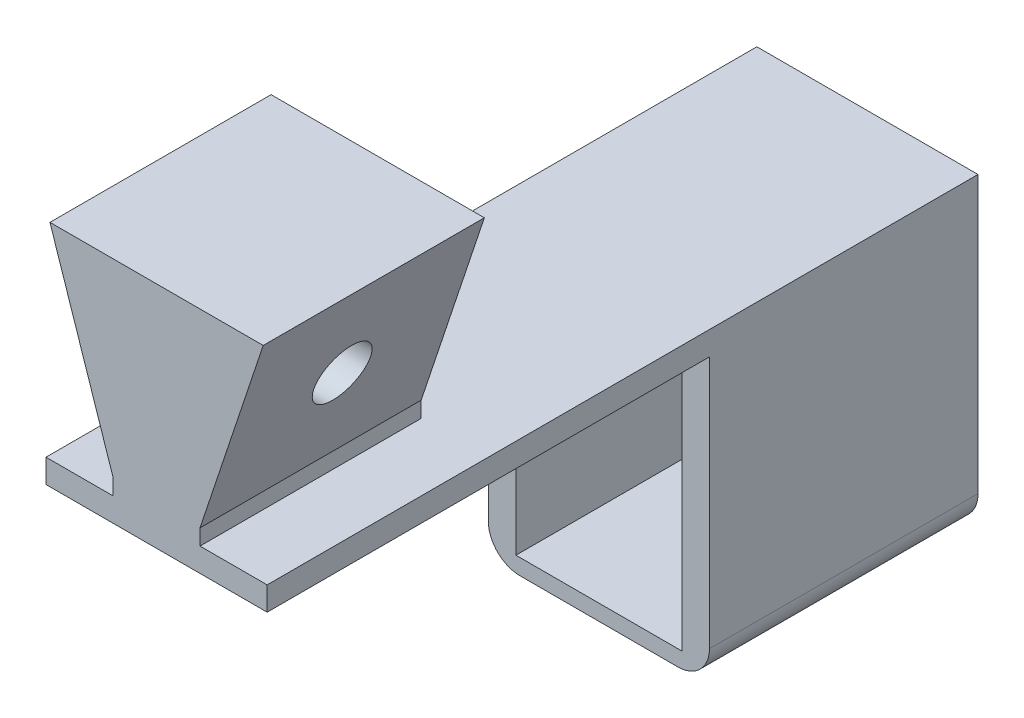
SolidWorks part; units mm, degrees
ref_plane "Front Plane" through (0, 0, 0) normal (0, 0, 1) x (1, 0, 0)
ref_plane "Top Plane" through (0, 0, 0) normal (0, 1, 0) x (1, 0, 0)
ref_plane "Right Plane" through (0, 0, 0) normal (1, 0, 0) x (0, 0, -1)
sketch "Sketch1" plane through (0, 0, 0) normal (0, 0, 1) x (1, 0, 0)
  line L0 (0, 0) -> (5.5, 0)
  line L1 (5.5, 0) -> (5.5, 1)
  line L2 (5.5, 1) -> (9.5, 13)
  line L3 (9.5, 13) -> (-4, 13)
  line L4 (-4, 13) -> (0, 1)
  line L5 (0, 1) -> (0, 0)
  dimension "D1" = 13.5
  dimension "D2" = 5.5
  dimension "D3" = 4
  dimension "D4" = 13
  dimension "D5" = 12
  dimension "D6" = 12
extrude "Boss-Extrude1" add sketch "Sketch1" along normal blind 14
hole_wizard "M3 Clearance Hole1" positions "Sketch2" profile "Sketch3" hole size "M3" standard "ANSI Metric" end condition up to next
sketch "Sketch2" plane through (0, 0, 0) normal (1, 0, 0) x (0, 0, -1)
  line L0 (0, 1) -> (0, 13) construction
  line L1 (-14, 0) -> (0, 0) construction
  point P0 (-7, 7)
  dimension "D1" = 7
  dimension "D2" = 7
sketch "Sketch3" plane through (0, 7, 7) normal (0, 1, 0) x (0, 0, 1)
  line L0 (0, 0) -> (0, 7.5)
  line L1 (0, 7.5) -> (1.8, 7.5)
  line L2 (1.8, 7.5) -> (1.8, 0)
  line L5 (1.8, 0) -> (0, 0)
  line L11 (0, -6.35) -> (0, 107.95) construction
  dimension "Thru Hole Dia." = 3.6
  dimension "Thru Hole Depth" = 7.5
sketch "Sketch4" plane through (0, 0, 0) normal (0, -1, 0) x (1, 0, 0)
  line L0 (-4, 14) -> (0, 14) construction
  line L1 (-4.25, 14) -> (9.75, 14)
  line L2 (-4.25, 14) -> (-4.25, -31)
  line L3 (-4.25, -31) -> (9.75, -31)
  line L4 (9.75, 14) -> (9.75, -31)
  line L5 (0, 14) -> (0, 0) construction
  dimension "D1" = 14
  dimension "D2" = 4.25
  dimension "D3" = 45
extrude "Boss-Extrude2" add sketch "Sketch4" along normal blind 1.5
sketch "Sketch5" plane through (0, -1.5, 0) normal (0, -1, 0) x (1, 0, 0)
  line L0 (9.75, -31) -> (9.75, 14) construction
  line L1 (9.75, -14) -> (8, -14)
  line L2 (9.75, -14) -> (9.75, -31)
  line L3 (9.75, -31) -> (8, -31)
  line L4 (8, -14) -> (8, -31)
  line L5 (-4.25, -31) -> (9.75, -31) construction
  line L6 (-4.25, 14) -> (-4.25, -31) construction
  line L7 (-4.25, -14) -> (-2.5, -14)
  line L8 (-4.25, -14) -> (-4.25, -31)
  line L9 (-4.25, -31) -> (-2.5, -31)
  line L10 (-2.5, -14) -> (-2.5, -31)
  dimension "D1" = 17
  dimension "D2" = 1.75
  dimension "D3" = 1.75
  dimension "D4" = 17
extrude "Boss-Extrude3" add sketch "Sketch5" along normal blind 17
sketch "Sketch6" plane through (0, -18.5, 0) normal (0, -1, 0) x (1, 0, 0)
  line L1 (-4.25, -14) -> (9.75, -14)
  line L2 (-4.25, -14) -> (-4.25, -31)
  line L3 (-4.25, -31) -> (9.75, -31)
  line L4 (9.75, -14) -> (9.75, -31)
extrude "Boss-Extrude4" add sketch "Sketch6" along normal blind 1
hole_wizard "M3 Clearance Hole2" positions "Sketch7" profile "Sketch8" hole size "M3" standard "ANSI Metric" end condition up to next
sketch "Sketch7" plane through (-4.25, 0, 0) normal (-1, 0, 0) x (0, 0, 1)
  line L1 (-14, -19.5) -> (-31, -19.5) construction
  line L2 (0, 13) -> (0, 1) construction
  point P0 (-24.75, -8.5)
  dimension "D1" = 24.75
  dimension "D2" = 11
sketch "Sketch8" plane through (-4.25, -8.5, -24.75) normal (0, 1, 0) x (0, 0, 1)
  line L0 (0, 0) -> (0, 1.75)
  line L1 (0, 1.75) -> (1.8, 1.75)
  line L2 (1.8, 1.75) -> (1.8, 0)
  line L5 (1.8, 0) -> (0, 0)
  line L11 (0, -6.35) -> (0, 107.95) construction
  dimension "Thru Hole Dia." = 3.6
  dimension "Thru Hole Depth" = 1.75
fillet "Fillet1" radius 2 2 edges at (9.75, -19.5, -22.5) (-4.25, -19.5, -22.5)
